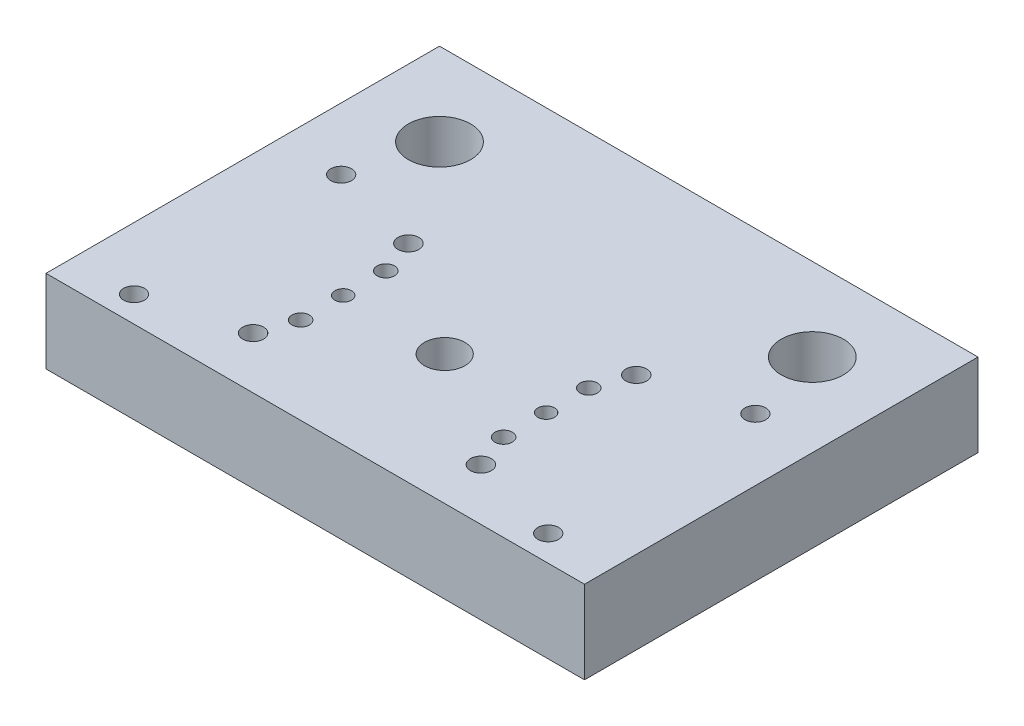
SolidWorks part; units mm, degrees
material "Plain Carbon Steel"
ref_plane "Front Plane" through (0, 0, 0) normal (0, 0, 1) x (1, 0, 0)
ref_plane "Top Plane" through (0, 0, 0) normal (0, 1, 0) x (1, 0, 0)
ref_plane "Right Plane" through (0, 0, 0) normal (1, 0, 0) x (0, 0, -1)
sketch "Sketch1" plane through (0, 0, 0) normal (0, 1, 0) x (1, 0, 0)
  line L0 (-130, 30) -> (130, 30) construction
  line L1 (-130, -95) -> (130, -95)
  line L2 (-130, -95) -> (-130, 95)
  line L3 (-130, 95) -> (130, 95)
  line L4 (130, -95) -> (130, 95)
  line L5 (-130, -95) -> (130, 95) construction
  line L6 (-130, 95) -> (130, -95) construction
  point P0 (0, 0)
  dimension "D1" = 260
  dimension "D2" = 190
  dimension "D3" = 125
extrude "Boss-Extrude1" add sketch "Sketch1" against normal blind 40
sketch "Sketch2" plane through (0, 0, 0) normal (0, 1, 0) x (1, 0, 0)
  line L0 (0, -95) -> (0, 95) construction
  line L1 (-130, -95) -> (130, -95) construction
  line L2 (130, 95) -> (-130, 95) construction
  circle A0 centre (-90, 55) radius 15
  circle A1 centre (90, 55) radius 15
  dimension "D2" = 30
  dimension "D1" = 180
  dimension "D3" = 150
extrude "Cut-Extrude1" cut sketch "Sketch2" against normal through all
ref_plane "Centre" through (0, 0, 32.5) normal (0, 0, 1) x (1, 0, 0)
sketch "Sketch3" plane through (0, -40, 0) normal (0, -1, 0) x (1, 0, 0)
  circle A0 centre (-55, 70) radius 5.05
  circle A1 centre (55, 70) radius 5.05
  circle A2 centre (55, -5) radius 5.05
  circle A3 centre (-55, -5) radius 5.05
  dimension "D1" = 10.1
extrude "Cut-Extrude2" cut sketch "Sketch3" against normal through all
sketch "Sketch4" plane through (0, -40, 0) normal (0, -1, 0) x (1, 0, 0)
  circle A2 centre (0, 32.5) radius 9.7705
  circle A3 centre (0, 32.5) radius 9.7705
  dimension "D1" = 3.2
extrude "Cut-Extrude3" cut sketch "Sketch4" against normal through all
hole_wizard "CBORE for M8 Hex Socket Head Cap Screw1" positions "Sketch11" profile "Sketch6" counterbore size "M8" standard "ISO" end condition through all
sketch "Sketch11" plane through (0, -40, 0) normal (0, -1, 0) x (-1, 0, 0)
  point P0 (-49, -11.95)
  point P3 (-49, -53.05)
  point P6 (49, -53.05)
  point P9 (49, -11.95)
sketch "Sketch6" plane through (49, -40, 11.95) normal (1, 0, 0) x (0, 0, -1)
  line L0 (0, 0) -> (0, 40)
  line L1 (0, 40) -> (4.2, 40)
  line L3 (4.2, 40) -> (4.2, 8.6)
  line L4 (4.2, 8.6) -> (7.5, 8.6)
  line L5 (7.5, 8.6) -> (7.5, 0)
  line L7 (7.5, 0) -> (0, 0)
  line L11 (0, -6.35) -> (0, 107.95) construction
  dimension "Thru Hole Dia." = 8.4
  dimension "Thru Hole Depth" = 40
  dimension "C'Bore Dia." = 15
  dimension "C'Bore Depth" = 8.6
hole_wizard "Ø8.0mm Dowel Hole1" positions "Sketch10" profile "Sketch9" hole size "Ø8.0" standard "ISO" end condition through all
sketch "Sketch10" plane through (0, -40, 0) normal (0, -1, 0) x (-1, 0, 0)
  point P0 (-49, -32.5)
  point P3 (49, -32.5)
sketch "Sketch9" plane through (49, -40, 32.5) normal (1, 0, 0) x (0, 0, -1)
  line L0 (0, 0) -> (0, 40)
  line L1 (0, 40) -> (4, 40)
  line L2 (4, 40) -> (4, 0)
  line L5 (4, 0) -> (0, 0)
  line L11 (0, -6.35) -> (0, 107.95) construction
  dimension "Thru Hole Dia." = 8
  dimension "Thru Hole Depth" = 40
hole_wizard "Ø10.0mm Dowel Hole1" positions "Sketch14" profile "Sketch13" hole size "Ø10.0" standard "ISO" end condition through all
sketch "Sketch14" plane through (0, -40, 0) normal (0, -1, 0) x (-1, 0, 0)
  point P0 (-100, 17.5)
  point P3 (-100, -82.5)
  point P6 (100, -82.5)
  point P9 (100, 17.5)
sketch "Sketch13" plane through (100, -40, -17.5) normal (1, 0, 0) x (0, 0, -1)
  line L0 (0, 0) -> (0, 40)
  line L1 (0, 40) -> (5, 40)
  line L2 (5, 40) -> (5, 0)
  line L5 (5, 0) -> (0, 0)
  line L11 (0, -6.35) -> (0, 107.95) construction
  dimension "Thru Hole Dia." = 10
  dimension "Thru Hole Depth" = 40
sketch "Sketch15" plane through (0, -40, 0) normal (0, -1, 0) x (1, 0, 0)
  circle A0 centre (-100, 82.5) radius 8.5
  circle A1 centre (100, 82.5) radius 8.5
  circle A2 centre (100, -17.5) radius 8.5
  circle A3 centre (-100, -17.5) radius 8.5
  dimension "D1" = 17
extrude "Cut-Extrude4" cut sketch "Sketch15" against normal blind 31.9
